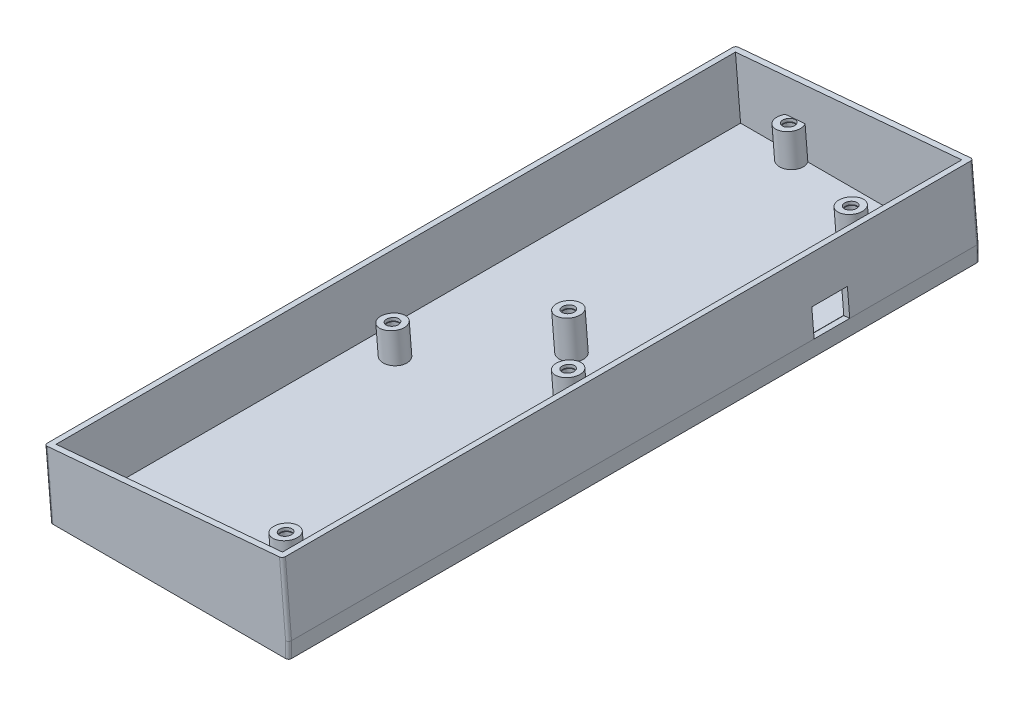
SolidWorks part; units mm, degrees
ref_plane "Alzado" through (0, 0, 0) normal (0, 0, 1) x (1, 0, 0)
ref_plane "Planta" through (0, 0, 0) normal (0, 1, 0) x (1, 0, 0)
ref_plane "Vista lateral" through (0, 0, 0) normal (1, 0, 0) x (0, 0, -1)
sketch "Croquis1" plane through (0, 0, 0) normal (0, 0, 1) x (1, 0, 0)
  line L0 (0, 0) -> (82.3502, 0) construction
  line L1 (82.3502, 0) -> (82.3502, 5.2293)
  line L2 (82.3502, 5.2293) -> (80.2933, 28.7395)
  line L4 (0, 21.7148) -> (0, 0) construction
  line L5 (80.2933, 28.7395) -> (78.3009, 28.5652)
  line L6 (78.3009, 28.5652) -> (1.9924, 21.8891)
  line L7 (1.9924, 21.8891) -> (0, 21.7148)
  line L8 (82.3502, 5.2293) -> (22.5785, 0) construction
  line L9 (78.3009, 28.5652) -> (80.3578, 5.055) construction
  line L10 (0, 21.7148) -> (1.8998, 0)
  line L11 (1.8998, 0) -> (82.3502, 0)
  dimension "D1" = 5
  dimension "D2" = 2
  dimension "D3" = 76.6
  dimension "D4" = 23.6
  dimension "D5" = 60
  dimension "D6" = 21.7148
extrude "Saliente-Extruir1" add sketch "Croquis1" along normal blind 233
shell "Vaciado1" thickness 2 removed face at (40.1466, 25.2272, 116.5)
ref_plane "Plano1" through (-0.9092, 10.3925, 0) normal (-0.0872, 0.9962, 0) x (0.9962, 0.0872, 0)
sketch "Croquis3" plane through (-0.9092, 10.3925, 0) normal (-0.0872, 0.9962, 0) x (0.9962, 0.0872, 0)
  line L0 (4.0926, -2) -> (80.2926, -2) construction
  line L3 (80.4926, -2) -> (3.8926, -2) construction
  line L4 (80.4926, -2.2) -> (80.4926, -230.8) construction
  line L5 (80.4926, -231) -> (80.4926, -2) construction
  line L6 (80.4926, -4.2) -> (23.1426, -4.2) construction
  line L7 (23.1426, -4.2) -> (23.1426, -2) construction
  line L8 (80.4926, -21.25) -> (61.2426, -21.25) construction
  line L9 (61.2426, -21.25) -> (61.2426, -2) construction
  line L10 (80.4926, -97.45) -> (42.1926, -97.45) construction
  line L11 (42.1926, -97.45) -> (42.1926, -2) construction
  line L12 (80.4926, -116.5) -> (61.2426, -116.5) construction
  line L13 (61.2426, -116.5) -> (61.2426, -21.25) construction
  line L14 (80.4926, -128.26) -> (13.6226, -128.26) construction
  line L15 (13.6226, -128.26) -> (13.6226, -2) construction
  line L16 (80.4926, -211.75) -> (61.2426, -211.75) construction
  line L17 (61.2426, -211.75) -> (61.2426, -116.5) construction
  line L18 (80.4926, -228.8) -> (23.1426, -228.8) construction
  line L19 (23.1426, -228.8) -> (23.1426, -4.2) construction
  circle A0 centre (23.1426, -4.2) radius 4
  circle A1 centre (61.2426, -21.25) radius 4
  circle A2 centre (42.1926, -97.45) radius 4
  circle A3 centre (61.2426, -116.5) radius 4
  circle A4 centre (13.6226, -128.26) radius 4
  circle A5 centre (23.1426, -228.8) radius 4
  circle A6 centre (61.2426, -211.75) radius 4
  point P4 (42.1926, -2)
  point P5 (42.1926, -2)
  point P6 (13.6226, -2)
  point P7 (23.1426, -2)
  point P8 (42.1926, -2)
  point P9 (61.2426, -2)
  point P14 (80.4926, -116.5)
  point P15 (80.4926, -116.5)
  point P16 (80.4926, -21.25)
  point P17 (80.4926, -97.45)
  point P18 (80.4926, -116.5)
  point P19 (80.4926, -128.26)
  point P20 (80.4926, -211.75)
  point P21 (80.4926, -228.8)
  point P22 (80.4926, -4.2)
  dimension "D14" = 8
  dimension "D1" = 76.2
  dimension "D2" = 9.53
  dimension "D3" = 19.05
  dimension "D4" = 38.1
  dimension "D5" = 57.15
  dimension "D6" = 228.6
  dimension "D7" = 19.05
  dimension "D8" = 95.25
  dimension "D9" = 114.3
  dimension "D10" = 126.06
  dimension "D11" = 209.55
  dimension "D12" = 226.6
  dimension "D13" = 2
extrude "Saliente-Extruir2" add sketch "Croquis3" against normal up to surface (10.0993 mm away) up to face at (42.0413, 2, 116.5)
sketch "Croquis4" plane through (-0.9092, 10.3925, 0) normal (-0.0872, 0.9962, 0) x (0.9962, 0.0872, 0)
  circle A0 centre (23.1426, -4.2) radius 1.5
  circle A1 centre (61.2426, -21.25) radius 1.5
  circle A2 centre (42.1926, -97.45) radius 1.5
  circle A3 centre (61.2426, -116.5) radius 1.5
  circle A4 centre (13.6226, -128.26) radius 1.5
  circle A5 centre (61.2426, -211.75) radius 1.5
  circle A6 centre (23.1426, -228.8) radius 1.5
  dimension "D1" = 3
extrude "Cortar-Extruir1" cut sketch "Croquis4" against normal blind 10
sketch "Croquis5" plane through (-0.9092, 10.3925, 0) normal (-0.0872, 0.9962, 0) x (0.9962, 0.0872, 0)
  circle A0 centre (23.1426, -4.2) radius 1.75
  circle A1 centre (61.2426, -21.25) radius 1.75
  circle A2 centre (42.1926, -97.45) radius 1.75
  circle A3 centre (61.2426, -116.5) radius 1.75
  circle A4 centre (13.6226, -128.26) radius 1.75
  circle A5 centre (23.1426, -228.8) radius 1.75
  circle A6 centre (61.2426, -211.75) radius 1.75
  dimension "D1" = 3.5
extrude "Cortar-Extruir2" cut sketch "Croquis5" against normal blind 5
sketch "Croquis6" plane through (-0.9092, 10.3925, 0) normal (-0.0872, 0.9962, 0) x (0.9962, 0.0872, 0)
  circle A0 centre (13.6226, -128.26) radius 2
  circle A1 centre (23.1426, -228.8) radius 2
  circle A2 centre (61.2426, -211.75) radius 2
  circle A3 centre (61.2426, -116.5) radius 2
  circle A4 centre (42.1926, -97.45) radius 2
  circle A5 centre (61.2426, -21.25) radius 2
  circle A6 centre (23.1426, -4.2) radius 2
  dimension "D1" = 4
extrude "Cortar-Extruir3" cut sketch "Croquis6" against normal blind 1
sketch "Croquis7" plane through (82.1787, 7.1897, 0) normal (0.9962, 0.0872, 0) x (0, 0, -1)
  line L0 (-230.8, -1.9678) -> (-2.2, -1.9678) construction
  line L1 (-233, -1.9678) -> (0, -1.9678) construction
  line L3 (-55.83, -1.9678) -> (-43.83, -1.9678)
  line L4 (-55.83, -1.9678) -> (-55.83, 7.0322)
  line L5 (-55.83, 7.0322) -> (-43.83, 7.0322)
  line L6 (-43.83, -1.9678) -> (-43.83, 7.0322)
  point P2 (-116.5, -1.9678)
  point P5 (-116.5, -1.9678)
  point P6 (-49.83, -1.9678)
  point P11 (-49.83, -1.9678)
  dimension "D1" = 228.6
  dimension "D2" = 47.63
  dimension "D3" = 12
  dimension "D4" = 9
extrude "Cortar-Extruir4" cut sketch "Croquis7" against normal up to surface (2 mm away) up to face at (79.3255, 16.8536, 116.5)
fillet "Redondeo1" radius 1 6 edges at (0.9499, 10.8574, 0) (82.3502, 2.6147, 0) (81.3217, 16.9844, 0) (0.9499, 10.8574, 233) (81.3217, 16.9844, 233) (82.3502, 2.6147, 233)
